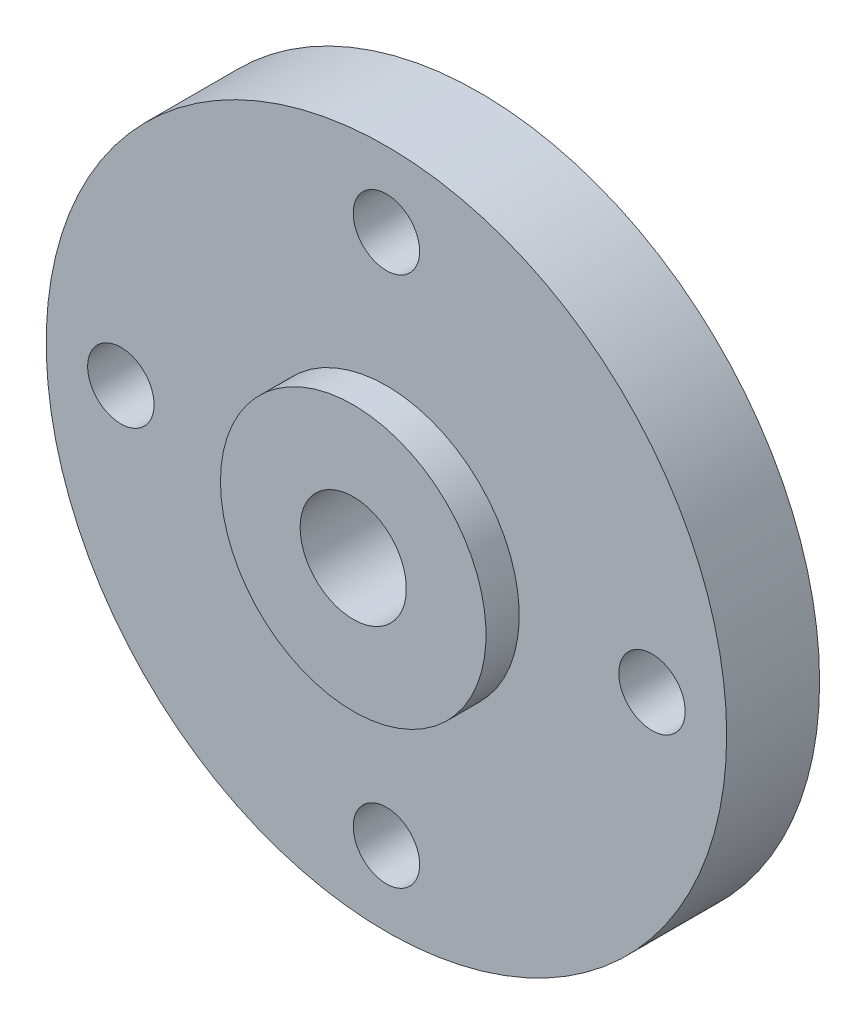
SolidWorks part; units mm, degrees
material "PMMA"
ref_plane "前视基准面" through (0, 0, 0) normal (0, 0, 1) x (1, 0, 0)
ref_plane "上视基准面" through (0, 0, 0) normal (0, 1, 0) x (1, 0, 0)
ref_plane "右视基准面" through (0, 0, 0) normal (1, 0, 0) x (0, 0, -1)
other "Configuration Table"
sketch "Sketch1" plane through (0, 0, 0) normal (0, 0, 1) x (1, 0, 0)
  circle A0 centre (0, 0) radius 10.25
  circle A1 centre (0, 0) radius 4
  circle A2 centre (0, 0) radius 1.6
extrude "Boss-Extrude1" add sketch "Sketch1" along normal blind 2.8 contours A0 A1 region at (-9.9601, 0, 0)
extrude "Boss-Extrude2" add sketch "Sketch1<3>" along normal blind 3.8 contours A1 A2 region at (-3.8869, 0, 0)
sketch "Sketch1<3>" plane through (0, 0, 0) normal (0, 0, 1) x (1, 0, 0) same geometry as "Sketch1"
sketch "Sketch2" plane through (0, 0, 2.8) normal (0, 0, 1) x (1, 0, 0)
  circle A0 centre (0, 0) radius 8
  circle A1 centre (0, 8) radius 1
  circle A2 centre (8, 0) radius 1
  circle A3 centre (0, -8) radius 1
  circle A4 centre (-8, 0) radius 1
extrude "Cut-Extrude1" cut sketch "Sketch2" against normal blind 2.8 contours A0 A1 | A0 A1 | A0 A4 | A0 A4 | A0 A3 | A0 A3 | A0 A2 | A0 A2 region at (7.5645, 0, 2.8) region at (8.413, 0, 2.8) region at (0, 7.5645, 2.8) region at (0, 8.413, 2.8) region at (0, -8.413, 2.8) region at (0, -7.5645, 2.8) region at (-7.5645, 0, 2.8) region at (-8.413, 0, 2.8)
